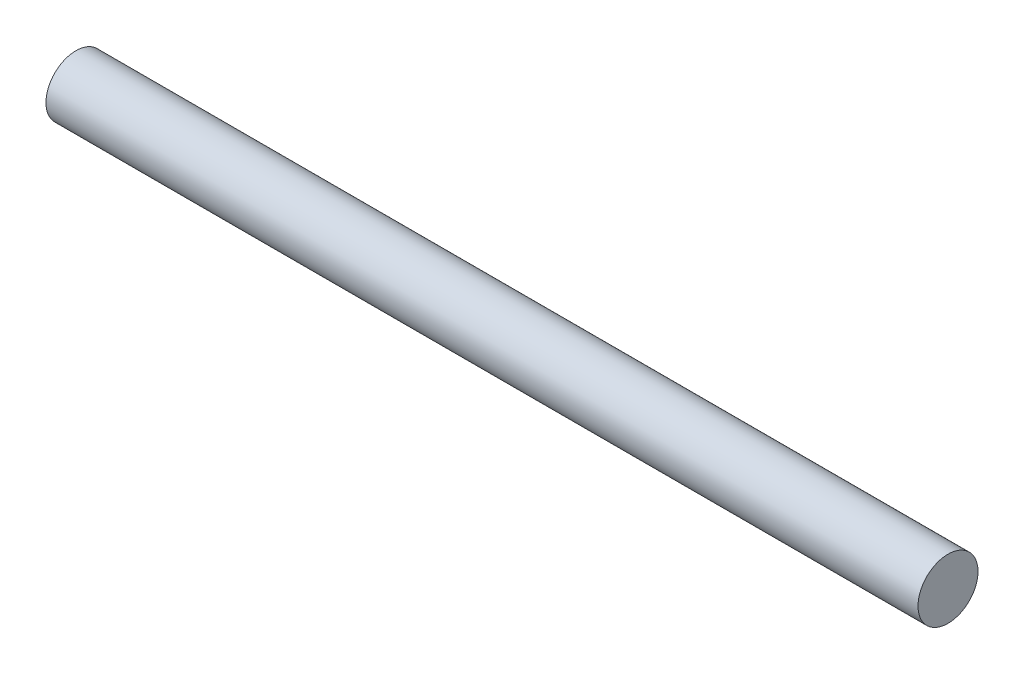
SolidWorks part; units mm, degrees
material "6061 Alloy"
ref_plane "Front Plane" through (0, 0, 0) normal (0, 0, 1) x (1, 0, 0)
ref_plane "Top Plane" through (0, 0, 0) normal (0, 1, 0) x (1, 0, 0)
ref_plane "Right Plane" through (0, 0, 0) normal (1, 0, 0) x (0, 0, -1)
sketch "Sketch1" plane through (0, 0, 0) normal (1, 0, 0) x (0, 0, -1)
  circle A0 centre (0, 0) radius 3
  dimension "D1" = 6
extrude "Boss-Extrude1" add sketch "Sketch1" along normal blind 87.2
